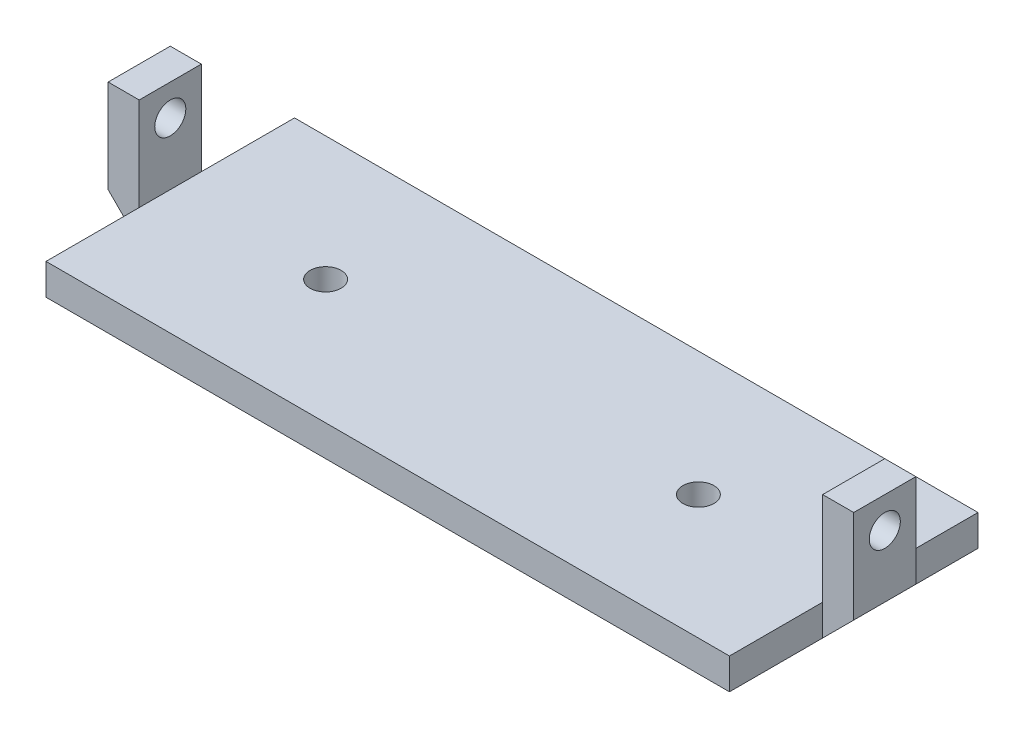
SolidWorks part; units mm, degrees
ref_plane "Front Plane" through (0, 0, 0) normal (0, 0, 1) x (1, 0, 0)
ref_plane "Top Plane" through (0, 0, 0) normal (0, 1, 0) x (1, 0, 0)
ref_plane "Right Plane" through (0, 0, 0) normal (1, 0, 0) x (0, 0, -1)
sketch "Sketch1" plane through (0, 0, 0) normal (0, 1, 0) x (1, 0, 0)
  line L1 (-60, 42.5) -> (60, 42.5)
  line L2 (-60, 42.5) -> (-60, -42.5)
  line L3 (-60, -42.5) -> (60, -42.5)
  line L4 (60, 42.5) -> (60, -42.5)
  line L5 (-60, 42.5) -> (60, -42.5) construction
  line L6 (-60, -42.5) -> (60, 42.5) construction
  point P0 (0, 0)
  dimension "D1" = 120
  dimension "D2" = 85
extrude "Boss-Extrude1" add sketch "Sketch1" along normal blind 5
sketch "Sketch2" plane through (0, 5, 0) normal (0, 1, 0) x (1, 0, 0)
  line L0 (-60, 42.5) -> (-60, -42.5) construction
  line L1 (-60, 17.5) -> (-55, 17.5)
  line L2 (-60, 17.5) -> (-60, 7.5)
  line L3 (-60, 7.5) -> (-55, 7.5)
  line L4 (-55, 17.5) -> (-55, 7.5)
  line L6 (-60, -7.5) -> (-55, -7.5)
  line L7 (-60, -7.5) -> (-60, -17.5)
  line L8 (-60, -17.5) -> (-55, -17.5)
  line L9 (-55, -7.5) -> (-55, -17.5)
  line L10 (-60, 12.5) -> (-55, 12.5) construction
  line L11 (-60, -12.5) -> (-55, -12.5) construction
  line L14 (60, 42.5) -> (-60, 42.5) construction
  line L16 (0, 0) -> (0, -27.3364) construction
  line L17 (60, -12.5) -> (55, -12.5) construction
  line L18 (60, 12.5) -> (55, 12.5) construction
  line L19 (55, -7.5) -> (55, -17.5)
  line L20 (60, -17.5) -> (55, -17.5)
  line L21 (60, -7.5) -> (60, -17.5)
  line L22 (60, -7.5) -> (55, -7.5)
  line L23 (55, 17.5) -> (55, 7.5)
  line L24 (60, 7.5) -> (55, 7.5)
  line L25 (60, 17.5) -> (60, 7.5)
  line L26 (60, 17.5) -> (55, 17.5)
  dimension "D1" = 30
  dimension "D2" = 10
  dimension "D3" = 10
  dimension "D4" = 25
  dimension "D5" = 5
  dimension "D6" = 5
extrude "Boss-Extrude2" add sketch "Sketch2" along normal blind 15
sketch "Sketch3" plane through (-60, 0, 0) normal (-1, 0, 0) x (0, 0, 1)
  line L0 (7.5, 20) -> (17.5, 20) construction
  line L1 (-17.5, 20) -> (-7.5, 20) construction
  line L2 (-17.5, 20) -> (-17.5, 5) construction
  line L3 (7.5, 20) -> (7.5, 5) construction
  circle A0 centre (-12.5, 15) radius 2.5
  circle A1 centre (12.5, 15) radius 2.5
  dimension "D1" = 5
  dimension "D2" = 5
  dimension "D3" = 5
  dimension "D4" = 5
  dimension "D5" = 5
  dimension "D6" = 5
extrude "Cut-Extrude1" cut sketch "Sketch3" against normal through all
sketch "Sketch5" plane through (0, 5, 0) normal (0, 1, 0) x (1, 0, 0)
  line L0 (0, 0) -> (0, -37.502) construction
  line L1 (-60, 42.5) -> (-55, 42.5)
  line L2 (-60, 42.5) -> (-60, 17.5)
  line L3 (-60, 17.5) -> (-55, 17.5)
  line L4 (-55, 42.5) -> (-55, 17.5)
  line L5 (-60, 7.5) -> (-55, 7.5)
  line L6 (-60, 7.5) -> (-60, -7.5)
  line L7 (-60, -7.5) -> (-55, -7.5)
  line L8 (-55, 7.5) -> (-55, -7.5)
  line L9 (-55, -17.5) -> (-60, -17.5)
  line L10 (-55, -17.5) -> (-55, -42.5)
  line L11 (-55, -42.5) -> (-60, -42.5)
  line L12 (-60, -17.5) -> (-60, -42.5)
  line L13 (60, -17.5) -> (60, -42.5)
  line L14 (55, -42.5) -> (60, -42.5)
  line L15 (55, -17.5) -> (55, -42.5)
  line L16 (55, -17.5) -> (60, -17.5)
  line L17 (55, 7.5) -> (55, -7.5)
  line L18 (60, -7.5) -> (55, -7.5)
  line L19 (60, 7.5) -> (60, -7.5)
  line L20 (60, 7.5) -> (55, 7.5)
  line L21 (55, 42.5) -> (55, 17.5)
  line L22 (60, 17.5) -> (55, 17.5)
  line L23 (60, 42.5) -> (60, 17.5)
  line L24 (60, 42.5) -> (55, 42.5)
extrude "Cut-Extrude2" cut sketch "Sketch5" against normal through all
chamfer "Chamfer1" distance 5 angle 45 4 edges at (-60, 0, 12.5) (-60, 0, -12.5) (60, 0, -12.5) (60, 0, 12.5)
sketch "Sketch6" plane through (0, 0, 0) normal (0, -1, 0) x (1, 0, 0)
  line L0 (-55, 42.5) -> (-55, 17.5) construction
  line L1 (-55, -42.5) -> (55, -42.5)
  line L2 (-55, -42.5) -> (-55, -7.5)
  line L3 (-55, -7.5) -> (55, -7.5)
  line L4 (55, -42.5) -> (55, -7.5)
  line L5 (55, 42.5) -> (-55, 42.5)
  line L6 (55, 42.5) -> (55, 32.5)
  line L7 (55, 32.5) -> (-55, 32.5)
  line L8 (-55, 42.5) -> (-55, 32.5)
  line L10 (-60, 17.5) -> (-55, 17.5) construction
  line L12 (-60, -7.5) -> (-55, -7.5)
  line L13 (-60, -7.5) -> (-60, -42.5)
  line L14 (-60, -42.5) -> (-55, -42.5)
  line L15 (-55, -7.5) -> (-55, -42.5)
  line L16 (55, -42.5) -> (60, -42.5)
  line L17 (55, -42.5) -> (55, -7.5)
  line L18 (55, -7.5) -> (60, -7.5)
  line L19 (60, -42.5) -> (60, -7.5)
  line M2 (-55, 42.5) -> (-55, 17.5)
  line M5 (-55, -7.5) -> (-55, -17.5)
  line M6 (-55, -17.5) -> (-55, -42.5)
  line M7 (-55, -42.5) -> (55, -42.5)
  line M8 (55, -42.5) -> (55, -17.5)
  line M9 (55, -17.5) -> (55, -7.5)
  line M12 (55, 17.5) -> (55, 42.5)
  line M13 (55, 42.5) -> (-55, 42.5)
  dimension "D1" = 15
extrude "Cut-Extrude3" cut sketch "Sketch6" against normal through all contours L3 M5 M6 M7 M8 M9 | L13 L14 L12 M6 M5 | L7 M12 M13 M2 | L16 L19 L18 M9 M8 region at (0, 0, -25) region at (-57.5, 0, -25) region at (57.5, 0, -25) region at (0, 0, 37.5)
sketch "Sketch7" plane through (0, 0, 0) normal (0, -1, 0) x (1, 0, 0)
  line L0 (-55, 17.5) -> (-55, 7.5) construction
  line L1 (55, 7.5) -> (55, 17.5) construction
  line L2 (55, 32.5) -> (-55, 32.5) construction
  circle A0 centre (-30, 12.5) radius 2.5
  circle A1 centre (30, 12.5) radius 2.5
  dimension "D1" = 5
  dimension "D2" = 5
  dimension "D3" = 25
  dimension "D4" = 25
  dimension "D5" = 20
  dimension "D6" = 20
extrude "Cut-Extrude4" cut sketch "Sketch7" against normal blind 10
